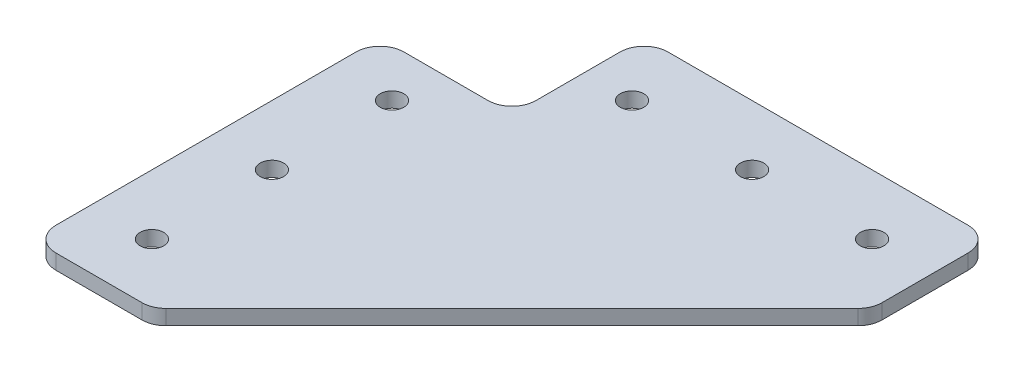
SolidWorks part; units mm, degrees
material "6061-T6 (SS)"
ref_plane "Front Plane" through (0, 0, 0) normal (0, 0, 1) x (1, 0, 0)
ref_plane "Top Plane" through (0, 0, 0) normal (0, 1, 0) x (1, 0, 0)
ref_plane "Right Plane" through (0, 0, 0) normal (1, 0, 0) x (0, 0, -1)
sketch "Sketch1" plane through (0, 0, 0) normal (0, 1, 0) x (1, 0, 0)
  line L0 (0, 0) -> (0, 101.6)
  line L1 (0, 101.6) -> (101.6, 101.6)
  line L3 (0, 0) -> (25.4, 0)
  line L4 (25.4, 0) -> (101.6, 76.2)
  line L5 (101.6, 76.2) -> (101.6, 101.6)
  dimension "D1" = 101.6
  dimension "D2" = 101.6
  dimension "D3" = 25.4
  dimension "D4" = 25.4
extrude "Boss-Extrude1" add sketch "Sketch1" along normal blind 3.175
sketch "Sketch2" plane through (0, 3.175, 0) normal (0, 1, 0) x (1, 0, 0)
  line L0 (101.6, 101.6) -> (0, 101.6) construction
  line L1 (0, 101.6) -> (0, 0) construction
  circle A0 centre (12.7, 88.9) radius 2.4892
  circle A1 centre (38.1, 88.9) radius 2.4892
  circle A2 centre (63.5, 88.9) radius 2.4892
  circle A3 centre (88.9, 88.9) radius 2.4892
  circle A4 centre (12.7, 63.5) radius 2.4892
  circle A5 centre (12.7, 38.1) radius 2.4892
  circle A6 centre (12.7, 12.7) radius 2.4892
  dimension "D1" = 25.4
  dimension "D2" = 12.7
  dimension "D3" = 25.4
  dimension "D4" = 25.4
  dimension "D5" = 25.4
  dimension "D6" = 25.4
  dimension "D7" = 25.4
  dimension "D8" = 12.7
  dimension "D9" = 4.9784
extrude "Cut-Extrude1" cut sketch "Sketch2" against normal through all
sketch "Sketch3" plane through (0, 3.175, 0) normal (0, 1, 0) x (1, 0, 0)
  line L1 (0, 101.6) -> (27.94, 101.6)
  line L2 (0, 101.6) -> (0, 73.66)
  line L3 (0, 73.66) -> (27.94, 73.66)
  line L4 (27.94, 101.6) -> (27.94, 73.66)
  dimension "D1" = 27.94
extrude "Cut-Extrude2" cut sketch "Sketch3" against normal through all
fillet "Fillet1" radius 5.08 7 edges at (0, 1.5875, 0) (25.4, 1.5875, 0) (101.6, 1.5875, -76.2) (101.6, 1.5875, -101.6) (27.94, 1.5875, -101.6) (0, 1.5875, -73.66) (27.94, 1.5875, -73.66)
